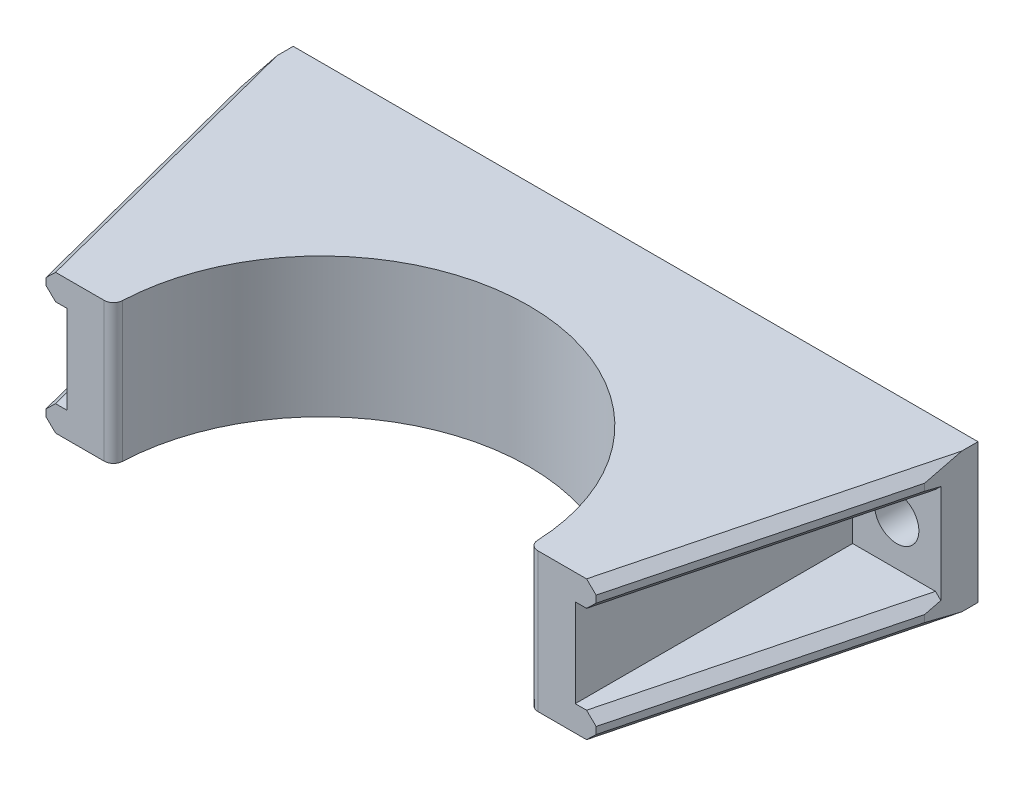
SolidWorks part; units mm, degrees
ref_plane "Front Plane" through (0, 0, 0) normal (0, 0, 1) x (1, 0, 0)
ref_plane "Top Plane" through (0, 0, 0) normal (0, 1, 0) x (1, 0, 0)
ref_plane "Right Plane" through (0, 0, 0) normal (1, 0, 0) x (0, 0, -1)
sketch "Sketch1" plane through (0, 0, 0) normal (0, 1, 0) x (1, 0, 0)
  line L0 (-54.75, -11.5) -> (-54.75, -56.25)
  line L2 (-54.75, -11.5) -> (-54.75, 3.5)
  line L3 (-54.75, 11.5) -> (54.75, 11.5)
  line L4 (54.75, -11.5) -> (54.75, 3.5)
  line L5 (-54.75, -11.5) -> (54.75, 11.5) construction
  line L6 (-54.75, 11.5) -> (0, 0) construction
  line L7 (-54.75, -56.25) -> (-44.75, -56.25)
  line L8 (54.75, -56.25) -> (54.75, -11.5)
  line L9 (44.75, -56.25) -> (54.75, -56.25)
  line L11 (-54.75, 11.5) -> (-73.75, 11.5)
  line L13 (-54.75, 3.5) -> (-73.75, 3.5)
  line L14 (-73.75, 11.5) -> (-73.75, 3.5)
  line L15 (54.75, 11.5) -> (73.75, 11.5)
  line L17 (54.75, 3.5) -> (73.75, 3.5)
  line L18 (73.75, 11.5) -> (73.75, 3.5)
  arc A0 (44.75, -56.25) -> (-44.75, -56.25) centre (0, -56.25) ccw
  point P0 (0, 0)
  dimension "D3" = 89.5
  dimension "D1" = 10
  dimension "D2" = 23
  dimension "D4" = 10
  dimension "D5" = 109.5
  dimension "D6" = 0
  dimension "D7" = 19
  dimension "D8" = 19
  dimension "D9" = 8
  dimension "D10" = 8
extrude "Boss-Extrude1" add sketch "Sketch1" along normal blind 30
sketch "Sketch8" plane through (0, 0, -3.5) normal (0, 0, 1) x (1, 0, 0)
  circle A0 centre (-64.25, 15) radius 4.7625
  circle A1 centre (64.25, 15) radius 4.7625
  dimension "D1" = 9.525
  dimension "D2" = 9.525
extrude "Cut-Extrude2" cut sketch "Sketch8" against normal through all both and the other way through all
sketch "Sketch9" plane through (0, 0, -3.5) normal (0, 0, 1) x (1, 0, 0)
  line L0 (-54.75, 30) -> (-54.75, 0) construction
  line L1 (-73.75, 30) -> (-54.75, 30)
  line L2 (-73.75, 30) -> (-73.75, 24.5)
  line L3 (-73.75, 24.5) -> (-54.75, 24.5)
  line L4 (-54.75, 30) -> (-54.75, 24.5)
  line L5 (54.75, 30) -> (54.75, 0) construction
  line L6 (-73.75, 0) -> (-54.75, 0)
  line L7 (-73.75, 0) -> (-73.75, 5.5)
  line L8 (-73.75, 5.5) -> (-54.75, 5.5)
  line L9 (-54.75, 0) -> (-54.75, 5.5)
  line L10 (73.75, 30) -> (54.75, 30)
  line L11 (73.75, 30) -> (73.75, 24.5)
  line L12 (73.75, 24.5) -> (54.75, 24.5)
  line L13 (54.75, 30) -> (54.75, 24.5)
  line L15 (73.75, 0) -> (54.75, 0)
  line L16 (73.75, 0) -> (73.75, 5.5)
  line L17 (73.75, 5.5) -> (54.75, 5.5)
  line L18 (54.75, 0) -> (54.75, 5.5)
extrude "Boss-Extrude3" add sketch "Sketch9" along normal up to surface (59.75 mm away) up to face at (-49.75, 15, 56.25)
sketch "Sketch10" plane through (0, 30, 0) normal (0, 1, 0) x (1, 0, 0)
  line L0 (-59.25, -56.25) -> (-73.75, 0)
  line L1 (-73.75, -56.25) -> (-44.75, -56.25) construction
  line L2 (-73.75, 11.5) -> (-73.75, -56.25) construction
  line L3 (-73.75, 0) -> (-73.75, -56.25)
  line L4 (-73.75, -56.25) -> (-59.25, -56.25)
  line L5 (73.75, -56.25) -> (59.25, -56.25)
  line L6 (44.75, -56.25) -> (73.75, -56.25) construction
  line L7 (59.25, -56.25) -> (73.75, 0)
  line L8 (73.75, -56.25) -> (73.75, 11.5) construction
  line L9 (73.75, 0) -> (73.75, -56.25)
extrude "Cut-Extrude3" cut sketch "Sketch10" against normal through all both and the other way through all
chamfer "Chamfer4" distance 2 angle 45 8 edges at (66.5, 24.5, 28.125) (66.5, 5.5, 28.125) (66.5, 0, 28.125) (-66.5, 0, 28.125) (-66.5, 5.5, 28.125) (-66.5, 24.5, 28.125)
fillet "Fillet2" radius 2 2 edges at (44.75, 15, 56.25) (-44.75, 15, 56.25)
